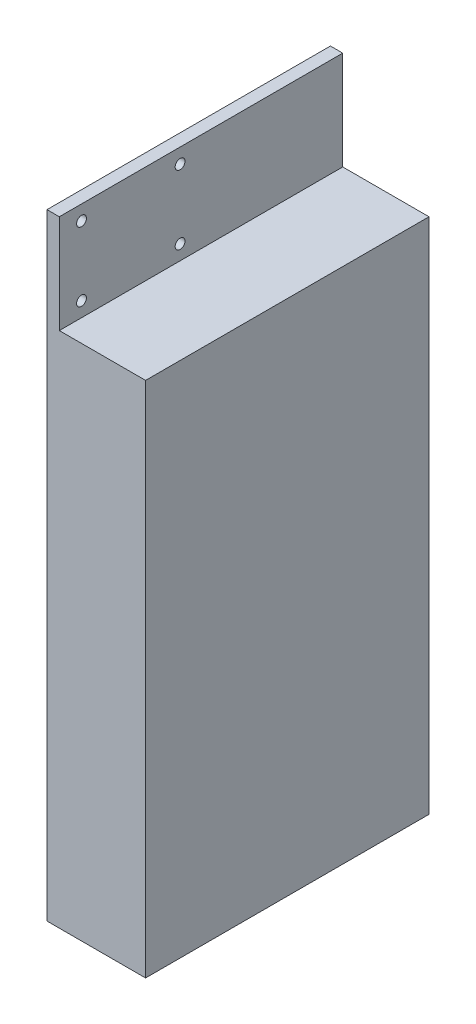
SolidWorks part; units mm, degrees
ref_plane "Front Plane" through (0, 0, 0) normal (0, 0, 1) x (1, 0, 0)
ref_plane "Top Plane" through (0, 0, 0) normal (0, 1, 0) x (1, 0, 0)
ref_plane "Right Plane" through (0, 0, 0) normal (1, 0, 0) x (0, 0, -1)
sketch "Sketch1" plane through (0, 0, 0) normal (0, 0, 1) x (1, 0, 0)
  line L0 (0, 0) -> (0, 40)
  line L1 (0, 40) -> (-5, 40)
  line L2 (-5, 40) -> (-5, -210)
  line L3 (-5, -210) -> (35, -210)
  line L4 (35, -210) -> (35, 0)
  line L5 (0, 0) -> (35, 0)
  point P6 (0, 0)
  dimension "D1" = 5
  dimension "D2" = 40
  dimension "D3" = 250
  dimension "D4" = 35
extrude "Boss-Extrude1" add sketch "Sketch1" along normal blind 115
sketch "Sketch2" plane through (-5, 0, 0) normal (-1, 0, 0) x (0, 0, 1)
  line L0 (106, 40) -> (106, 34) construction
  line L1 (115, 40) -> (0, 40) construction
  line L2 (115, 40) -> (115, -210) construction
  line L3 (106, 34) -> (66, 34) construction
  line L4 (106, 34) -> (106, 20) construction
  line L5 (106, 20) -> (115, 20) construction
  circle A0 centre (106, 34) radius 2
  circle A1 centre (66, 34) radius 2
  circle A2 centre (66, 6) radius 2
  circle A3 centre (106, 6) radius 2
  dimension "D4" = 4
  dimension "D5" = 4
  dimension "D1" = 6
  dimension "D2" = 9
  dimension "D3" = 40
  dimension "D6" = 28
extrude "Cut-Extrude1" cut sketch "Sketch2" against normal through all
